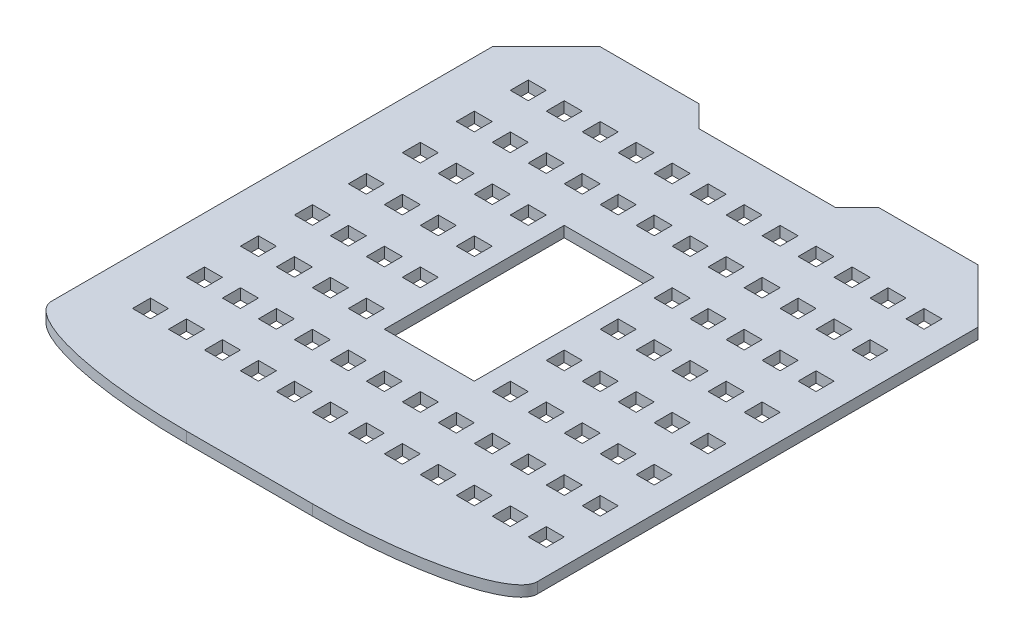
SolidWorks part; units mm, degrees
material "Balsa"
ref_plane "Front Plane" through (0, 0, 0) normal (0, 0, 1) x (1, 0, 0)
ref_plane "Top Plane" through (0, 0, 0) normal (0, 1, 0) x (1, 0, 0)
ref_plane "Right Plane" through (0, 0, 0) normal (1, 0, 0) x (0, 0, -1)
sketch "Sketch1" plane through (0, 0, 0) normal (0, 1, 0) x (1, 0, 0)
  line L1 (-67.5, 75) -> (67.5, 75)
  line L2 (-67.5, 75) -> (-67.5, -75)
  line L3 (-67.5, -75) -> (67.5, -75)
  line L4 (67.5, 75) -> (67.5, -75)
  line L5 (-67.5, 75) -> (67.5, -75) construction
  line L6 (-67.5, -75) -> (67.5, 75) construction
  point P0 (0, 0)
  dimension "D1" = 135
  dimension "D2" = 150
extrude "Boss-Extrude1" add sketch "Sketch1" along normal blind 3
sketch "Sketch2" plane through (0, 3, 0) normal (0, 1, 0) x (1, 0, 0)
  line L0 (-67.5, 75) -> (-67.5, -75) construction
  line L1 (-54.5, 52) -> (-49.5, 52)
  line L2 (-54.5, 52) -> (-54.5, 57)
  line L3 (-54.5, 57) -> (-49.5, 57)
  line L4 (-49.5, 52) -> (-49.5, 57)
  line L5 (-54.5, 52) -> (-49.5, 57) construction
  line L6 (-54.5, 57) -> (-49.5, 52) construction
  line L7 (67.5, 75) -> (-67.5, 75) construction
  line L732 (-44.5, 52) -> (-44.5, 57)
  line L733 (-44.5, 52) -> (-39.5, 52)
  line L734 (-39.5, 52) -> (-39.5, 57)
  line L735 (-44.5, 57) -> (-39.5, 57)
  line L736 (-34.5, 52) -> (-34.5, 57)
  line L737 (-34.5, 52) -> (-29.5, 52)
  line L738 (-29.5, 52) -> (-29.5, 57)
  line L739 (-34.5, 57) -> (-29.5, 57)
  line L740 (-24.5, 52) -> (-24.5, 57)
  line L741 (-24.5, 52) -> (-19.5, 52)
  line L742 (-19.5, 52) -> (-19.5, 57)
  line L743 (-24.5, 57) -> (-19.5, 57)
  line L744 (-14.5, 52) -> (-14.5, 57)
  line L745 (-14.5, 52) -> (-9.5, 52)
  line L746 (-9.5, 52) -> (-9.5, 57)
  line L747 (-14.5, 57) -> (-9.5, 57)
  line L748 (-4.5, 52) -> (-4.5, 57)
  line L749 (-4.5, 52) -> (0.5, 52)
  line L750 (0.5, 52) -> (0.5, 57)
  line L751 (-4.5, 57) -> (0.5, 57)
  line L752 (5.5, 52) -> (5.5, 57)
  line L753 (5.5, 52) -> (10.5, 52)
  line L754 (10.5, 52) -> (10.5, 57)
  line L755 (5.5, 57) -> (10.5, 57)
  line L756 (15.5, 52) -> (15.5, 57)
  line L757 (15.5, 52) -> (20.5, 52)
  line L758 (20.5, 52) -> (20.5, 57)
  line L759 (15.5, 57) -> (20.5, 57)
  line L760 (25.5, 52) -> (25.5, 57)
  line L761 (25.5, 52) -> (30.5, 52)
  line L762 (30.5, 52) -> (30.5, 57)
  line L763 (25.5, 57) -> (30.5, 57)
  line L764 (35.5, 52) -> (35.5, 57)
  line L765 (35.5, 52) -> (40.5, 52)
  line L766 (40.5, 52) -> (40.5, 57)
  line L767 (35.5, 57) -> (40.5, 57)
  line L768 (45.5, 52) -> (45.5, 57)
  line L769 (45.5, 52) -> (50.5, 52)
  line L770 (50.5, 52) -> (50.5, 57)
  line L771 (45.5, 57) -> (50.5, 57)
  line L772 (55.5, 52) -> (55.5, 57)
  line L773 (55.5, 52) -> (60.5, 52)
  line L774 (60.5, 52) -> (60.5, 57)
  line L775 (55.5, 57) -> (60.5, 57)
  line L780 (-44.5, 37) -> (-44.5, 42)
  line L781 (-44.5, 37) -> (-39.5, 37)
  line L782 (-39.5, 37) -> (-39.5, 42)
  line L783 (-44.5, 42) -> (-39.5, 42)
  line L784 (-34.5, 37) -> (-34.5, 42)
  line L785 (-34.5, 37) -> (-29.5, 37)
  line L786 (-29.5, 37) -> (-29.5, 42)
  line L787 (-34.5, 42) -> (-29.5, 42)
  line L788 (-24.5, 37) -> (-24.5, 42)
  line L789 (-24.5, 37) -> (-19.5, 37)
  line L790 (-19.5, 37) -> (-19.5, 42)
  line L791 (-24.5, 42) -> (-19.5, 42)
  line L792 (-14.5, 37) -> (-14.5, 42)
  line L793 (-14.5, 37) -> (-9.5, 37)
  line L794 (-9.5, 37) -> (-9.5, 42)
  line L795 (-14.5, 42) -> (-9.5, 42)
  line L796 (-4.5, 37) -> (-4.5, 42)
  line L797 (-4.5, 37) -> (0.5, 37)
  line L798 (0.5, 37) -> (0.5, 42)
  line L799 (-4.5, 42) -> (0.5, 42)
  line L800 (5.5, 37) -> (5.5, 42)
  line L801 (5.5, 37) -> (10.5, 37)
  line L802 (10.5, 37) -> (10.5, 42)
  line L803 (5.5, 42) -> (10.5, 42)
  line L804 (15.5, 37) -> (15.5, 42)
  line L805 (15.5, 37) -> (20.5, 37)
  line L806 (20.5, 37) -> (20.5, 42)
  line L807 (15.5, 42) -> (20.5, 42)
  line L808 (25.5, 37) -> (25.5, 42)
  line L809 (25.5, 37) -> (30.5, 37)
  line L810 (30.5, 37) -> (30.5, 42)
  line L811 (25.5, 42) -> (30.5, 42)
  line L812 (35.5, 37) -> (35.5, 42)
  line L813 (35.5, 37) -> (40.5, 37)
  line L814 (40.5, 37) -> (40.5, 42)
  line L815 (35.5, 42) -> (40.5, 42)
  line L816 (45.5, 37) -> (45.5, 42)
  line L817 (45.5, 37) -> (50.5, 37)
  line L818 (50.5, 37) -> (50.5, 42)
  line L819 (45.5, 42) -> (50.5, 42)
  line L820 (55.5, 37) -> (55.5, 42)
  line L821 (55.5, 37) -> (60.5, 37)
  line L822 (60.5, 37) -> (60.5, 42)
  line L823 (55.5, 42) -> (60.5, 42)
  line L828 (-44.5, 22) -> (-44.5, 27)
  line L829 (-44.5, 22) -> (-39.5, 22)
  line L830 (-39.5, 22) -> (-39.5, 27)
  line L831 (-44.5, 27) -> (-39.5, 27)
  line L832 (-34.5, 22) -> (-34.5, 27)
  line L833 (-34.5, 22) -> (-29.5, 22)
  line L834 (-29.5, 22) -> (-29.5, 27)
  line L835 (-34.5, 27) -> (-29.5, 27)
  line L836 (-24.5, 22) -> (-24.5, 27)
  line L837 (-24.5, 22) -> (-19.5, 22)
  line L838 (-19.5, 22) -> (-19.5, 27)
  line L839 (-24.5, 27) -> (-19.5, 27)
  line L840 (-14.5, 22) -> (-14.5, 27)
  line L841 (-14.5, 22) -> (-9.5, 22)
  line L842 (-9.5, 22) -> (-9.5, 27)
  line L843 (-14.5, 27) -> (-9.5, 27)
  line L844 (-4.5, 22) -> (-4.5, 27)
  line L845 (-4.5, 22) -> (0.5, 22)
  line L846 (0.5, 22) -> (0.5, 27)
  line L847 (-4.5, 27) -> (0.5, 27)
  line L848 (5.5, 22) -> (5.5, 27)
  line L849 (5.5, 22) -> (10.5, 22)
  line L850 (10.5, 22) -> (10.5, 27)
  line L851 (5.5, 27) -> (10.5, 27)
  line L852 (15.5, 22) -> (15.5, 27)
  line L853 (15.5, 22) -> (20.5, 22)
  line L854 (20.5, 22) -> (20.5, 27)
  line L855 (15.5, 27) -> (20.5, 27)
  line L856 (25.5, 22) -> (25.5, 27)
  line L857 (25.5, 22) -> (30.5, 22)
  line L858 (30.5, 22) -> (30.5, 27)
  line L859 (25.5, 27) -> (30.5, 27)
  line L860 (35.5, 22) -> (35.5, 27)
  line L861 (35.5, 22) -> (40.5, 22)
  line L862 (40.5, 22) -> (40.5, 27)
  line L863 (35.5, 27) -> (40.5, 27)
  line L864 (45.5, 22) -> (45.5, 27)
  line L865 (45.5, 22) -> (50.5, 22)
  line L866 (50.5, 22) -> (50.5, 27)
  line L867 (45.5, 27) -> (50.5, 27)
  line L868 (55.5, 22) -> (55.5, 27)
  line L869 (55.5, 22) -> (60.5, 22)
  line L870 (60.5, 22) -> (60.5, 27)
  line L871 (55.5, 27) -> (60.5, 27)
  line L876 (-44.5, 7) -> (-44.5, 12)
  line L877 (-44.5, 7) -> (-39.5, 7)
  line L878 (-39.5, 7) -> (-39.5, 12)
  line L879 (-44.5, 12) -> (-39.5, 12)
  line L880 (-34.5, 7) -> (-34.5, 12)
  line L881 (-34.5, 7) -> (-29.5, 7)
  line L882 (-29.5, 7) -> (-29.5, 12)
  line L883 (-34.5, 12) -> (-29.5, 12)
  line L884 (-24.5, 7) -> (-24.5, 12)
  line L885 (-24.5, 7) -> (-19.5, 7)
  line L886 (-19.5, 7) -> (-19.5, 12)
  line L887 (-24.5, 12) -> (-19.5, 12)
  line L888 (-14.5, 7) -> (-14.5, 12)
  line L889 (-14.5, 7) -> (-9.5, 7)
  line L890 (-9.5, 7) -> (-9.5, 12)
  line L891 (-14.5, 12) -> (-9.5, 12)
  line L892 (-4.5, 7) -> (-4.5, 12)
  line L893 (-4.5, 7) -> (0.5, 7)
  line L894 (0.5, 7) -> (0.5, 12)
  line L895 (-4.5, 12) -> (0.5, 12)
  line L896 (5.5, 7) -> (5.5, 12)
  line L897 (5.5, 7) -> (10.5, 7)
  line L898 (10.5, 7) -> (10.5, 12)
  line L899 (5.5, 12) -> (10.5, 12)
  line L900 (15.5, 7) -> (15.5, 12)
  line L901 (15.5, 7) -> (20.5, 7)
  line L902 (20.5, 7) -> (20.5, 12)
  line L903 (15.5, 12) -> (20.5, 12)
  line L904 (25.5, 7) -> (25.5, 12)
  line L905 (25.5, 7) -> (30.5, 7)
  line L906 (30.5, 7) -> (30.5, 12)
  line L907 (25.5, 12) -> (30.5, 12)
  line L908 (35.5, 7) -> (35.5, 12)
  line L909 (35.5, 7) -> (40.5, 7)
  line L910 (40.5, 7) -> (40.5, 12)
  line L911 (35.5, 12) -> (40.5, 12)
  line L912 (45.5, 7) -> (45.5, 12)
  line L913 (45.5, 7) -> (50.5, 7)
  line L914 (50.5, 7) -> (50.5, 12)
  line L915 (45.5, 12) -> (50.5, 12)
  line L916 (55.5, 7) -> (55.5, 12)
  line L917 (55.5, 7) -> (60.5, 7)
  line L918 (60.5, 7) -> (60.5, 12)
  line L919 (55.5, 12) -> (60.5, 12)
  line L924 (-44.5, -8) -> (-44.5, -3)
  line L925 (-44.5, -8) -> (-39.5, -8)
  line L926 (-39.5, -8) -> (-39.5, -3)
  line L927 (-44.5, -3) -> (-39.5, -3)
  line L928 (-34.5, -8) -> (-34.5, -3)
  line L929 (-34.5, -8) -> (-29.5, -8)
  line L930 (-29.5, -8) -> (-29.5, -3)
  line L931 (-34.5, -3) -> (-29.5, -3)
  line L932 (-24.5, -8) -> (-24.5, -3)
  line L933 (-24.5, -8) -> (-19.5, -8)
  line L934 (-19.5, -8) -> (-19.5, -3)
  line L935 (-24.5, -3) -> (-19.5, -3)
  line L936 (-14.5, -8) -> (-14.5, -3)
  line L937 (-14.5, -8) -> (-9.5, -8)
  line L938 (-9.5, -8) -> (-9.5, -3)
  line L939 (-14.5, -3) -> (-9.5, -3)
  line L940 (-4.5, -8) -> (-4.5, -3)
  line L941 (-4.5, -8) -> (0.5, -8)
  line L942 (0.5, -8) -> (0.5, -3)
  line L943 (-4.5, -3) -> (0.5, -3)
  line L944 (5.5, -8) -> (5.5, -3)
  line L945 (5.5, -8) -> (10.5, -8)
  line L946 (10.5, -8) -> (10.5, -3)
  line L947 (5.5, -3) -> (10.5, -3)
  line L948 (15.5, -8) -> (15.5, -3)
  line L949 (15.5, -8) -> (20.5, -8)
  line L950 (20.5, -8) -> (20.5, -3)
  line L951 (15.5, -3) -> (20.5, -3)
  line L952 (25.5, -8) -> (25.5, -3)
  line L953 (25.5, -8) -> (30.5, -8)
  line L954 (30.5, -8) -> (30.5, -3)
  line L955 (25.5, -3) -> (30.5, -3)
  line L956 (35.5, -8) -> (35.5, -3)
  line L957 (35.5, -8) -> (40.5, -8)
  line L958 (40.5, -8) -> (40.5, -3)
  line L959 (35.5, -3) -> (40.5, -3)
  line L960 (45.5, -8) -> (45.5, -3)
  line L961 (45.5, -8) -> (50.5, -8)
  line L962 (50.5, -8) -> (50.5, -3)
  line L963 (45.5, -3) -> (50.5, -3)
  line L964 (55.5, -8) -> (55.5, -3)
  line L965 (55.5, -8) -> (60.5, -8)
  line L966 (60.5, -8) -> (60.5, -3)
  line L967 (55.5, -3) -> (60.5, -3)
  line L972 (-44.5, -23) -> (-44.5, -18)
  line L973 (-44.5, -23) -> (-39.5, -23)
  line L974 (-39.5, -23) -> (-39.5, -18)
  line L975 (-44.5, -18) -> (-39.5, -18)
  line L976 (-34.5, -23) -> (-34.5, -18)
  line L977 (-34.5, -23) -> (-29.5, -23)
  line L978 (-29.5, -23) -> (-29.5, -18)
  line L979 (-34.5, -18) -> (-29.5, -18)
  line L980 (-24.5, -23) -> (-24.5, -18)
  line L981 (-24.5, -23) -> (-19.5, -23)
  line L982 (-19.5, -23) -> (-19.5, -18)
  line L983 (-24.5, -18) -> (-19.5, -18)
  line L984 (-14.5, -23) -> (-14.5, -18)
  line L985 (-14.5, -23) -> (-9.5, -23)
  line L986 (-9.5, -23) -> (-9.5, -18)
  line L987 (-14.5, -18) -> (-9.5, -18)
  line L988 (-4.5, -23) -> (-4.5, -18)
  line L989 (-4.5, -23) -> (0.5, -23)
  line L990 (0.5, -23) -> (0.5, -18)
  line L991 (-4.5, -18) -> (0.5, -18)
  line L992 (5.5, -23) -> (5.5, -18)
  line L993 (5.5, -23) -> (10.5, -23)
  line L994 (10.5, -23) -> (10.5, -18)
  line L995 (5.5, -18) -> (10.5, -18)
  line L996 (15.5, -23) -> (15.5, -18)
  line L997 (15.5, -23) -> (20.5, -23)
  line L998 (20.5, -23) -> (20.5, -18)
  line L999 (15.5, -18) -> (20.5, -18)
  line L1000 (25.5, -23) -> (25.5, -18)
  line L1001 (25.5, -23) -> (30.5, -23)
  line L1002 (30.5, -23) -> (30.5, -18)
  line L1003 (25.5, -18) -> (30.5, -18)
  line L1004 (35.5, -23) -> (35.5, -18)
  line L1005 (35.5, -23) -> (40.5, -23)
  line L1006 (40.5, -23) -> (40.5, -18)
  line L1007 (35.5, -18) -> (40.5, -18)
  line L1008 (45.5, -23) -> (45.5, -18)
  line L1009 (45.5, -23) -> (50.5, -23)
  line L1010 (50.5, -23) -> (50.5, -18)
  line L1011 (45.5, -18) -> (50.5, -18)
  line L1012 (55.5, -23) -> (55.5, -18)
  line L1013 (55.5, -23) -> (60.5, -23)
  line L1014 (60.5, -23) -> (60.5, -18)
  line L1015 (55.5, -18) -> (60.5, -18)
  line L1020 (-44.5, -38) -> (-44.5, -33)
  line L1021 (-44.5, -38) -> (-39.5, -38)
  line L1022 (-39.5, -38) -> (-39.5, -33)
  line L1023 (-44.5, -33) -> (-39.5, -33)
  line L1024 (-34.5, -38) -> (-34.5, -33)
  line L1025 (-34.5, -38) -> (-29.5, -38)
  line L1026 (-29.5, -38) -> (-29.5, -33)
  line L1027 (-34.5, -33) -> (-29.5, -33)
  line L1028 (-24.5, -38) -> (-24.5, -33)
  line L1029 (-24.5, -38) -> (-19.5, -38)
  line L1030 (-19.5, -38) -> (-19.5, -33)
  line L1031 (-24.5, -33) -> (-19.5, -33)
  line L1032 (-14.5, -38) -> (-14.5, -33)
  line L1033 (-14.5, -38) -> (-9.5, -38)
  line L1034 (-9.5, -38) -> (-9.5, -33)
  line L1035 (-14.5, -33) -> (-9.5, -33)
  line L1036 (-4.5, -38) -> (-4.5, -33)
  line L1037 (-4.5, -38) -> (0.5, -38)
  line L1038 (0.5, -38) -> (0.5, -33)
  line L1039 (-4.5, -33) -> (0.5, -33)
  line L1040 (5.5, -38) -> (5.5, -33)
  line L1041 (5.5, -38) -> (10.5, -38)
  line L1042 (10.5, -38) -> (10.5, -33)
  line L1043 (5.5, -33) -> (10.5, -33)
  line L1044 (15.5, -38) -> (15.5, -33)
  line L1045 (15.5, -38) -> (20.5, -38)
  line L1046 (20.5, -38) -> (20.5, -33)
  line L1047 (15.5, -33) -> (20.5, -33)
  line L1048 (25.5, -38) -> (25.5, -33)
  line L1049 (25.5, -38) -> (30.5, -38)
  line L1050 (30.5, -38) -> (30.5, -33)
  line L1051 (25.5, -33) -> (30.5, -33)
  line L1052 (35.5, -38) -> (35.5, -33)
  line L1053 (35.5, -38) -> (40.5, -38)
  line L1054 (40.5, -38) -> (40.5, -33)
  line L1055 (35.5, -33) -> (40.5, -33)
  line L1056 (45.5, -38) -> (45.5, -33)
  line L1057 (45.5, -38) -> (50.5, -38)
  line L1058 (50.5, -38) -> (50.5, -33)
  line L1059 (45.5, -33) -> (50.5, -33)
  line L1060 (55.5, -38) -> (55.5, -33)
  line L1061 (55.5, -38) -> (60.5, -38)
  line L1062 (60.5, -38) -> (60.5, -33)
  line L1063 (55.5, -33) -> (60.5, -33)
  line L1068 (-44.5, -53) -> (-44.5, -48)
  line L1069 (-44.5, -53) -> (-39.5, -53)
  line L1070 (-39.5, -53) -> (-39.5, -48)
  line L1071 (-44.5, -48) -> (-39.5, -48)
  line L1072 (-34.5, -53) -> (-34.5, -48)
  line L1073 (-34.5, -53) -> (-29.5, -53)
  line L1074 (-29.5, -53) -> (-29.5, -48)
  line L1075 (-34.5, -48) -> (-29.5, -48)
  line L1076 (-24.5, -53) -> (-24.5, -48)
  line L1077 (-24.5, -53) -> (-19.5, -53)
  line L1078 (-19.5, -53) -> (-19.5, -48)
  line L1079 (-24.5, -48) -> (-19.5, -48)
  line L1080 (-14.5, -53) -> (-14.5, -48)
  line L1081 (-14.5, -53) -> (-9.5, -53)
  line L1082 (-9.5, -53) -> (-9.5, -48)
  line L1083 (-14.5, -48) -> (-9.5, -48)
  line L1084 (-4.5, -53) -> (-4.5, -48)
  line L1085 (-4.5, -53) -> (0.5, -53)
  line L1086 (0.5, -53) -> (0.5, -48)
  line L1087 (-4.5, -48) -> (0.5, -48)
  line L1088 (5.5, -53) -> (5.5, -48)
  line L1089 (5.5, -53) -> (10.5, -53)
  line L1090 (10.5, -53) -> (10.5, -48)
  line L1091 (5.5, -48) -> (10.5, -48)
  line L1092 (15.5, -53) -> (15.5, -48)
  line L1093 (15.5, -53) -> (20.5, -53)
  line L1094 (20.5, -53) -> (20.5, -48)
  line L1095 (15.5, -48) -> (20.5, -48)
  line L1096 (25.5, -53) -> (25.5, -48)
  line L1097 (25.5, -53) -> (30.5, -53)
  line L1098 (30.5, -53) -> (30.5, -48)
  line L1099 (25.5, -48) -> (30.5, -48)
  line L1100 (35.5, -53) -> (35.5, -48)
  line L1101 (35.5, -53) -> (40.5, -53)
  line L1102 (40.5, -53) -> (40.5, -48)
  line L1103 (35.5, -48) -> (40.5, -48)
  line L1104 (45.5, -53) -> (45.5, -48)
  line L1105 (45.5, -53) -> (50.5, -53)
  line L1106 (50.5, -53) -> (50.5, -48)
  line L1107 (45.5, -48) -> (50.5, -48)
  line L1108 (55.5, -53) -> (55.5, -48)
  line L1109 (55.5, -53) -> (60.5, -53)
  line L1110 (60.5, -53) -> (60.5, -48)
  line L1111 (55.5, -48) -> (60.5, -48)
  line L1116 (-54.5, 37) -> (-54.5, 42)
  line L1117 (-54.5, 37) -> (-49.5, 37)
  line L1118 (-49.5, 37) -> (-49.5, 42)
  line L1119 (-54.5, 42) -> (-49.5, 42)
  line L1120 (-54.5, 22) -> (-54.5, 27)
  line L1121 (-54.5, 22) -> (-49.5, 22)
  line L1122 (-49.5, 22) -> (-49.5, 27)
  line L1123 (-54.5, 27) -> (-49.5, 27)
  line L1124 (-54.5, 7) -> (-54.5, 12)
  line L1125 (-54.5, 7) -> (-49.5, 7)
  line L1126 (-49.5, 7) -> (-49.5, 12)
  line L1127 (-54.5, 12) -> (-49.5, 12)
  line L1128 (-54.5, -8) -> (-54.5, -3)
  line L1129 (-54.5, -8) -> (-49.5, -8)
  line L1130 (-49.5, -8) -> (-49.5, -3)
  line L1131 (-54.5, -3) -> (-49.5, -3)
  line L1132 (-54.5, -23) -> (-54.5, -18)
  line L1133 (-54.5, -23) -> (-49.5, -23)
  line L1134 (-49.5, -23) -> (-49.5, -18)
  line L1135 (-54.5, -18) -> (-49.5, -18)
  line L1136 (-54.5, -38) -> (-54.5, -33)
  line L1137 (-54.5, -38) -> (-49.5, -38)
  line L1138 (-49.5, -38) -> (-49.5, -33)
  line L1139 (-54.5, -33) -> (-49.5, -33)
  line L1140 (-54.5, -53) -> (-54.5, -48)
  line L1141 (-54.5, -53) -> (-49.5, -53)
  line L1142 (-49.5, -53) -> (-49.5, -48)
  line L1143 (-54.5, -48) -> (-49.5, -48)
  line L1144 (-42, 75) -> (-42, -75) construction
  line L1145 (-67.5, -75) -> (67.5, -75) construction
  line L1147 (65.5, 52) -> (65.5, 57) [skipped]
  line L1148 (65.5, 52) -> (70.5, 52) [skipped]
  line L1149 (70.5, 52) -> (70.5, 57) [skipped]
  line L1150 (65.5, 57) -> (70.5, 57) [skipped]
  line L1151 (65.5, 37) -> (65.5, 42) [skipped]
  line L1152 (65.5, 37) -> (70.5, 37) [skipped]
  line L1153 (70.5, 37) -> (70.5, 42) [skipped]
  line L1154 (65.5, 42) -> (70.5, 42) [skipped]
  line L1155 (65.5, 22) -> (65.5, 27) [skipped]
  line L1156 (65.5, 22) -> (70.5, 22) [skipped]
  line L1157 (70.5, 22) -> (70.5, 27) [skipped]
  line L1158 (65.5, 27) -> (70.5, 27) [skipped]
  line L1159 (65.5, 7) -> (65.5, 12) [skipped]
  line L1160 (65.5, 7) -> (70.5, 7) [skipped]
  line L1161 (70.5, 7) -> (70.5, 12) [skipped]
  line L1162 (65.5, 12) -> (70.5, 12) [skipped]
  line L1163 (65.5, -8) -> (65.5, -3) [skipped]
  line L1164 (65.5, -8) -> (70.5, -8) [skipped]
  line L1165 (70.5, -8) -> (70.5, -3) [skipped]
  line L1166 (65.5, -3) -> (70.5, -3) [skipped]
  line L1167 (65.5, -23) -> (65.5, -18) [skipped]
  line L1168 (65.5, -23) -> (70.5, -23) [skipped]
  line L1169 (70.5, -23) -> (70.5, -18) [skipped]
  line L1170 (65.5, -18) -> (70.5, -18) [skipped]
  line L1171 (65.5, -38) -> (65.5, -33) [skipped]
  line L1172 (65.5, -38) -> (70.5, -38) [skipped]
  line L1173 (70.5, -38) -> (70.5, -33) [skipped]
  line L1174 (65.5, -33) -> (70.5, -33) [skipped]
  line L1175 (65.5, -53) -> (65.5, -48) [skipped]
  line L1176 (65.5, -53) -> (70.5, -53) [skipped]
  line L1177 (70.5, -53) -> (70.5, -48) [skipped]
  line L1178 (65.5, -48) -> (70.5, -48) [skipped]
  point P0 (-52, 54.5)
  dimension "D1" = 5
  dimension "D2" = 8
  dimension "D3" = 13
  dimension "D4" = 23
  dimension "D6" = 13
  dimension "D5" = 25.5
extrude "Cut-Extrude1" cut sketch "Sketch2" against normal through all
fillet "Fillet1" radius 12.5 1 edges at (-67.5, 1.5, 75) second distance 50 first distance on face at (-67.5, 1.5, 0)
fillet "Fillet2" radius 12.5 1 edges at (67.5, 1.5, 75) second distance 50 first distance on face at (67.5, 1.5, 0)
sketch "Sketch4" plane through (0, 3, 0) normal (0, 1, 0) x (1, 0, 0)
  line L0 (-67.5, 60) -> (-67.5, 75)
  line L1 (-67.5, 75) -> (-67.5, -62.5) construction
  line L2 (-67.5, 75) -> (-52.5, 75)
  line L3 (67.5, 75) -> (-67.5, 75) construction
  line L4 (-52.5, 75) -> (-67.5, 60)
  line L5 (0, 75) -> (0, -75) construction
  line L6 (-17.5, -75) -> (17.5, -75) construction
  line L7 (67.5, 75) -> (52.5, 75)
  line L8 (67.5, 60) -> (67.5, 75)
  line L9 (52.5, 75) -> (67.5, 60)
  dimension "D1" = 45
  dimension "D2" = 15
extrude "Cut-Extrude2" cut sketch "Sketch4" against normal through all
sketch "Sketch5" plane through (0, 3, 0) normal (0, 1, 0) x (1, 0, 0)
  line L6 (0, -75) -> (0, 75) construction
  line L7 (-17.5, -75) -> (17.5, -75) construction
  line L8 (52.5, 75) -> (-52.5, 75) construction
  line L9 (-25, 75) -> (25, 75)
  line L11 (-19, 69) -> (19, 69)
  line L13 (-25, 75) -> (9.8447, 59.8447) construction
  line L14 (-9.8447, 59.8447) -> (25, 75) construction
  line L15 (-25, 75) -> (-19, 69)
  line L16 (25, 75) -> (19, 69)
  point P0 (0, 64.1266)
  point P1 (0, 75)
  dimension "D1" = 50
  dimension "D2" = 45
  dimension "D3" = 6
extrude "Cut-Extrude3" cut sketch "Sketch5" against normal through all
sketch "Sketch6" plane through (0, 3, 0) normal (0, 1, 0) x (1, 0, 0)
  line L1 (-14.5, 27) -> (10.5, 27)
  line L2 (-14.5, 27) -> (-14.5, -23)
  line L3 (-14.5, -23) -> (10.5, -23)
  line L4 (10.5, 27) -> (10.5, -23)
extrude "Cut-Extrude4" cut sketch "Sketch6" against normal through all
